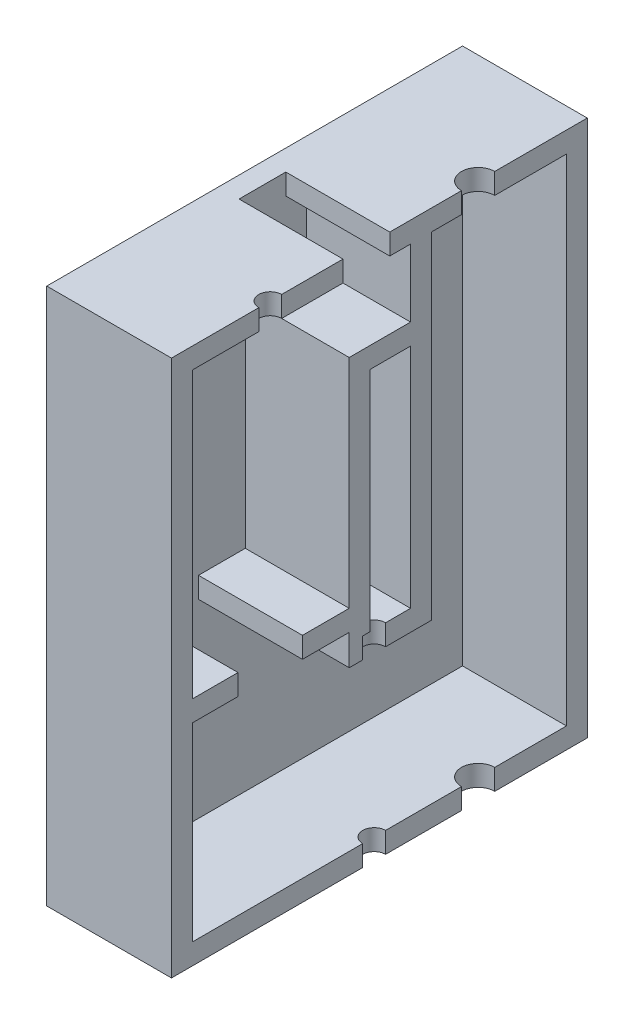
SolidWorks part; units mm, degrees
ref_plane "前视基准面" through (0, 0, 0) normal (0, 0, 1) x (1, 0, 0)
ref_plane "上视基准面" through (0, 0, 0) normal (0, 1, 0) x (1, 0, 0)
ref_plane "右视基准面" through (0, 0, 0) normal (1, 0, 0) x (0, 0, -1)
other "Configuration Table"
sketch "草图1" plane through (0, 0, 0) normal (1, 0, 0) x (0, 0, -1)
  line L1 (-20, 25.825) -> (20, 25.825)
  line L2 (-20, 25.825) -> (-20, -25.825)
  line L3 (-20, -25.825) -> (20, -25.825)
  line L4 (20, 25.825) -> (20, -25.825)
  line L5 (-20, 25.825) -> (20, -25.825) construction
  line L6 (-20, -25.825) -> (20, 25.825) construction
  point P0 (0, 0)
  dimension "D1" = 51.65
  dimension "D2" = 40
extrude "凸台-拉伸1" add sketch "草图1" along normal blind 12
shell "抽壳1" thickness 2 removed face at (12, 0, 0)
sketch "草图3" plane through (2, 0, 0) normal (1, 0, 0) x (0, 0, -1)
  line L19 (-2.9, 17.325) -> (3, 17.325)
  line L20 (-2.9, 17.325) -> (-2.9, -3.575)
  line L21 (-2.9, -8.525) -> (5, -8.525)
  line L22 (5, 17.175) -> (5, -8.525)
  line L23 (-3, 18.525) -> (-3, -3.475) construction
  line L24 (3.5, -8.725) -> (-4.5, -8.725) construction
  line L25 (8, 24.825) -> (8, -27.175) construction
  line L26 (18, 23.825) -> (-18, 23.825) construction
  line L27 (-18, 23.825) -> (-18, -23.825) construction
  line L28 (3, 23.825) -> (5, 23.825)
  line L29 (3, 23.825) -> (3, 17.325)
  line L31 (5, 23.825) -> (5, 17.175)
  line L32 (-0.9, 15.325) -> (3, 15.325)
  line L33 (-0.9, 15.325) -> (-0.9, -6.525)
  line L34 (-0.9, -6.525) -> (3, -6.525)
  line L35 (3, 15.325) -> (3, -6.525)
  line L36 (-18, -3.575) -> (-13.6, -3.575)
  line L37 (-18, -3.575) -> (-18, -5.575)
  line L38 (-18, -5.575) -> (-13.6, -5.575)
  line L39 (-13.6, -3.575) -> (-13.6, -5.575)
  line L40 (-18, -3.475) -> (-3, -3.475) construction
  line L41 (-7.4, -3.575) -> (-2.9, -3.575)
  line L42 (-7.4, -3.575) -> (-7.4, -5.575)
  line L43 (-7.4, -5.575) -> (-2.9, -5.575)
  line L45 (-7.5, -4.975) -> (-7.5, -3.475) construction
  line L46 (-13.5, -3.475) -> (-13.5, -4.975) construction
  line L48 (-2.9, -5.575) -> (-2.9, -8.525)
  dimension "D1" = 0.1
  dimension "D2" = 0.2
  dimension "D3" = 3
  dimension "D4" = 6.5
  dimension "D5" = 2
  dimension "D6" = 2
  dimension "D7" = 2
  dimension "D8" = 2
  dimension "D9" = 2
  dimension "D10" = 0.1
  dimension "D11" = 0.1
  dimension "D12" = 0.1
  dimension "D13" = 2
  dimension "D14" = 2
extrude "凸台-拉伸6" add sketch "草图3" along normal up to surface (10 mm away) up to face at (12, 0, 0)
sketch "草图4" plane through (0, 25.825, 0) normal (0, 1, 0) x (1, 0, 0)
  line L0 (2, 3) -> (2, -18) construction
  line L1 (12, 1) -> (2, 1)
  line L2 (12, 1) -> (12, -3.5)
  line L3 (12, -3.5) -> (2, -3.5)
  line L4 (2, 1) -> (2, -3.5)
  line L5 (12, -3.5) -> (22, -3.5) construction
  circle A1 centre (12, -10.5) radius 1.1
  circle A2 centre (12, 9.5) radius 1.6
  arc A3 (12, 7.9) -> (12, 11.1) centre (12, 9.5) ccw construction
  arc A4 (12, -11.6) -> (12, -9.4) centre (12, -10.5) ccw construction
extrude "切除-拉伸1" cut sketch "草图4" against normal up to next
sketch "草图5" plane through (0, -25.825, 0) normal (0, -1, 0) x (1, 0, 0)
  circle A0 centre (12, -9.5) radius 1.6
  circle A1 centre (12, 0.5) radius 1.1
  circle A2 centre (12, 0.5) radius 1 construction
  arc A3 (12, -7.9) -> (12, -11.1) centre (12, -9.5) ccw construction
  dimension "D1" = 0.1
extrude "切除-拉伸2" cut sketch "草图5" against normal blind 19.3
